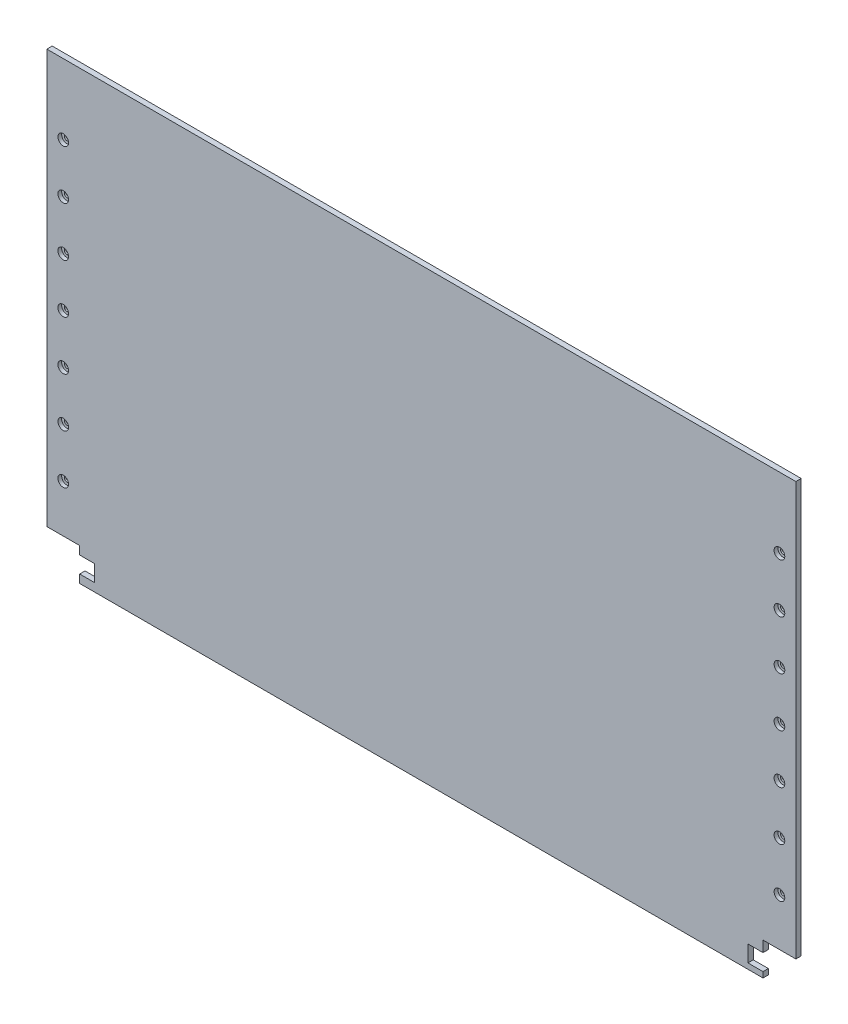
SolidWorks part; units mm, degrees
ref_plane "Plan de face" through (0, 0, 0) normal (0, 0, 1) x (1, 0, 0)
ref_plane "Plan de dessus" through (0, 0, 0) normal (0, 1, 0) x (1, 0, 0)
ref_plane "Plan de droite" through (0, 0, 0) normal (1, 0, 0) x (0, 0, -1)
sketch "Esquisse1" plane through (0, 0, 0) normal (0, 0, 1) x (1, 0, 0)
  line L0 (416, -251.75) -> (-416, -251.75)
  line L1 (-456, -251.75) -> (456, -251.75)
  line L2 (-456, -251.75) -> (-456, 251.75)
  line L3 (-456, 251.75) -> (456, 251.75)
  line L4 (456, -251.75) -> (456, 251.75)
  line L5 (-456, -251.75) -> (456, 251.75) construction
  line L6 (-456, 251.75) -> (456, -251.75) construction
  line L7 (416, -251.75) -> (416, -291.75)
  line L8 (-416, -251.75) -> (-416, -291.75)
  line L9 (416, -291.75) -> (-416, -291.75)
  line L10 (-416, -261.75) -> (-416, -281.75)
  line L11 (-416, -261.75) -> (-397.6701, -261.75)
  line L12 (-416, -281.75) -> (-397.6701, -281.75)
  line L13 (-397.6701, -261.75) -> (-397.6701, -281.75)
  line L14 (397.67, -285) -> (421.0907, -285)
  line L15 (421.0907, -265) -> (421.0907, -285)
  line L16 (397.67, -265) -> (421.0907, -265)
  line L17 (1229.67, -288.5) -> (397.67, -288.5)
  line L18 (397.67, -265) -> (397.67, -285)
  point P0 (0, 0)
  dimension "D1" = 912
  dimension "D2" = 503.5
  dimension "D3" = 40
  dimension "D4" = 40
  dimension "D5" = 40
  dimension "D6" = 10
  dimension "D7" = 20
  dimension "D8" = 18.3299
extrude "Boss.-Extru.1" add sketch "Esquisse1" along normal blind 6.5 contours L11 L13 L12 L8 L9 L7 L0 L18 L16 L15 L14 | L1 L4 L3 L2 L0 region at (0, -271.7134, 0) region at (0, 0, 0)
sketch "Esquisse2" plane through (0, 0, 6.5) normal (0, 0, 1) x (1, 0, 0)
  line L0 (-446, 245.25) -> (-428, 245.25)
  line L1 (-446, 245.25) -> (-446, 191.4632)
  line L2 (-428, 245.25) -> (-428, 191.4632)
  line L3 (-446, 191.4632) -> (-428, 191.4632)
  line L4 (-456, 251.75) -> (456, 251.75) construction
  dimension "D1" = 6.5
ref_point "Point1"
ref_axis "Axe1" through (0, 251.75, 3.25) along (0, 1, 0)
ref_plane "Plan1" through (0, 0, 0) normal (1, 0, 0) x (0, 1, 0)
hole_wizard "Dégagement M61" positions "Esquisse4" profile "Esquisse3" hole size "M6" standard "JIS" end condition through all
sketch "Esquisse4" plane through (0, 0, 0) normal (0, 0, -1) x (-1, 0, 0)
  point P0 (436.0253, 166.0315)
sketch "Esquisse3" plane through (-436.0253, 166.0315, 0) normal (1, 0, 0) x (0, 1, 0)
  line L0 (0, 0) -> (0, 6.5)
  line L1 (0, 6.5) -> (3.3, 6.5)
  line L2 (3.3, 6.5) -> (3.3, 0)
  line L5 (3.3, 0) -> (0, 0)
  line L11 (0, -6.35) -> (0, 107.95) construction
  dimension "Diamètre du perçage jusqu'au prochain" = 6.6
  dimension "Profondeur du perçage jusqu'au prochain" = 6.5
hole_wizard "Chambrage pour vis à tête ronde bombée M61" positions "Esquisse6" profile "Esquisse5" counterbore size "M6" standard "Ansi Metric" end condition through all
sketch "Esquisse6" plane through (0, 0, 6.5) normal (0, 0, 1) x (1, 0, 0)
  point P0 (-436.0253, 166.0315)
sketch "Esquisse5" plane through (-436.0253, 166.0315, 6.5) normal (1, 0, 0) x (0, -1, 0)
  line L0 (0, 0) -> (0, 6.5)
  line L1 (0, 6.5) -> (3.3, 6.5)
  line L2 (3.3, 4.625) -> (3.3, 6.5)
  line L3 (3.3, 4.625) -> (3.325, 4.6)
  line L4 (3.325, 4.6) -> (6.5, 4.6)
  line L5 (6.5, 4.6) -> (6.5, 0)
  line L7 (0, 0) -> (6.5, 0)
  line L9 (-3.3, 4.625) -> (-3.325, 4.6) construction
  line L11 (0, -6.35) -> (0, 107.95) construction
  dimension "Diamètre du perçage jusqu'au prochain" = 6.6
  dimension "Profondeur du perçage jusqu'au prochain" = 6.5
  dimension "Diamètre du chambrage" = 13
  dimension "Profondeur du chambrage" = 4.6
  dimension "Diamètre du fraisage milieu" = 6.65
  dimension "Angle du fraisage milieu" = 90
pattern_linear "Répétition linéaire1" count 7 spacing 60 along (0, -1, 0) of "Chambrage pour vis à tête ronde bombée M61"
mirror "Symétrie2" about plane through (0, 0, 0) normal (1, 0, 0) of "Répétition linéaire1"
